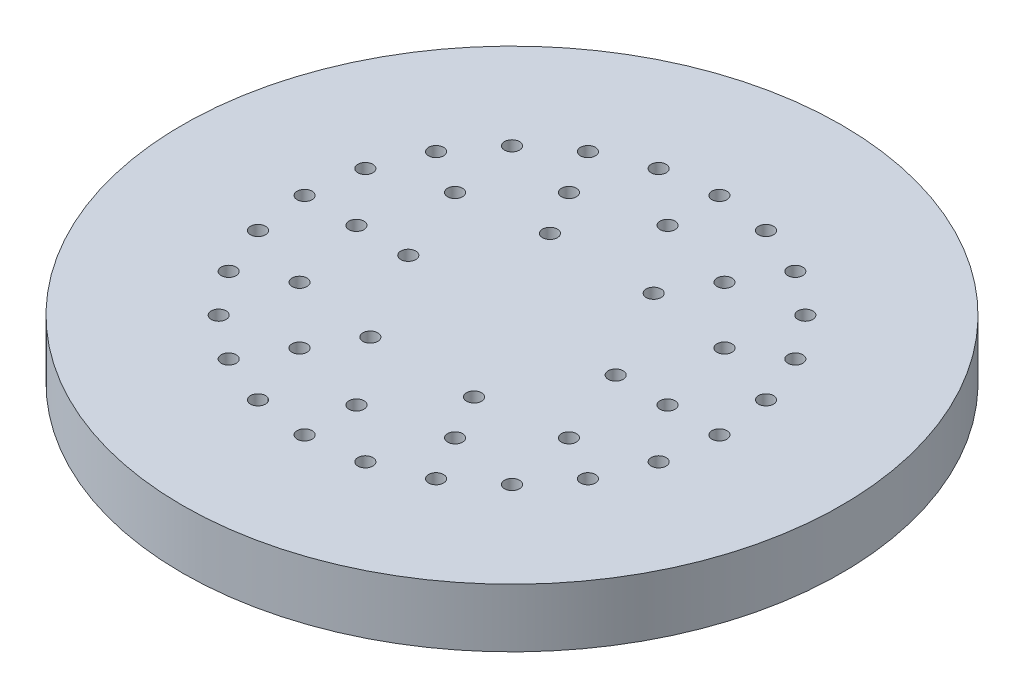
SolidWorks part; units mm, degrees
ref_plane "Front Plane" through (0, 0, 0) normal (0, 0, 1) x (1, 0, 0)
ref_plane "Top Plane" through (0, 0, 0) normal (0, 1, 0) x (1, 0, 0)
ref_plane "Right Plane" through (0, 0, 0) normal (1, 0, 0) x (0, 0, -1)
ref_axis "Axial" through (0, -55, 0) along (0, 1, 0)
ref_plane "Bottom Plane" through (0, -5.08, 0) normal (0, 1, 0) x (1, 0, 0)
sketch "Sketch1" plane through (0, 0, 0) normal (0, 1, 0) x (1, 0, 0)
  circle A0 centre (0, 0) radius 28.575
  dimension "D1" = 57.15
extrude "Billet" add sketch "Sketch1" against normal blind 5.08
sketch "Sketch2" plane through (0, 0, 0) normal (0, 1, 0) x (1, 0, 0)
  line L0 (0, 18.6449) -> (0, -20.0163) construction
  line L1 (-17.698, 0) -> (15.8694, 0) construction
  circle A0 centre (8.9916, 0) radius 0.6477
  circle A1 centre (13.4874, 0) radius 0.6477
  circle A2 centre (17.9832, 0) radius 0.6477
  dimension "D1" = 1.2954
  dimension "D2" = 8.9916
  dimension "D3" = 4.4958
  dimension "D4" = 4.4958
extrude "First Lox Hole" cut sketch "Sketch2" against normal through all
pattern_circular "CirPattern1" count 6 over 360 about axis through (0, -55, 0) along (0, 1, 0) of "First Lox Hole"
pattern_circular "CirPattern2" count 12 over 360 about axis through (0, -55, 0) along (0, 1, 0) skipping 2, 4, 6, 8, 10 of face at (13.4874, -5.08, 0.6477)
pattern_circular "CirPattern3" count 24 over 360 about axis through (0, -55, 0) along (0, 1, 0) skipping 4, 8, 12, 16, 20 of face at (17.9832, -5.08, 0.6477)
sketch "Sketch4" plane through (0, -5.08, 0) normal (0, 1, 0) x (1, 0, 0)
  line L0 (0, 30.8778) -> (0, -33.3039) construction
  line L1 (-2.794, 0) -> (2.794, 0) construction
  circle A0 centre (0, 25.4) radius 1.1906
  circle A1 centre (0, -25.4) radius 1.1906
  dimension "D1" = 2.3813
  dimension "D2" = 25.4
extrude "Dowel" cut sketch "Sketch4" along normal blind 3.175
sketch "Sketch5" plane through (0, 0, 0) normal (0, 1, 0) x (1, 0, 0)
  line L0 (0, 0) -> (-8.9916, 0) construction
  line L1 (0, 0) -> (0, 13.4874) construction
  line L2 (0, 0) -> (17.9832, 0) construction
  dimension "D1" = 8.9916
  dimension "D2" = 13.4874
  dimension "D3" = 17.9832
